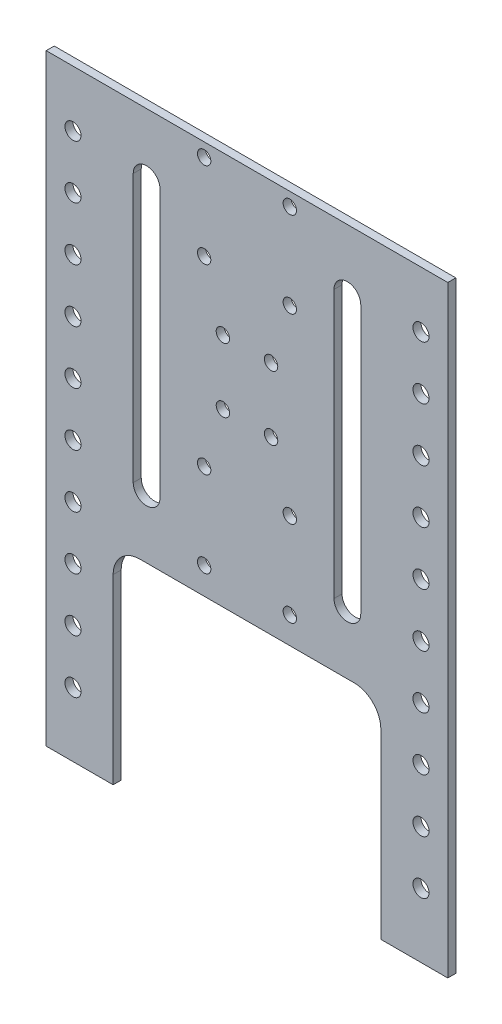
SolidWorks part; units mm, degrees
note: The reader was unsure of these and kept them because the rebuilt part matched: thickness of "Base-Flange1", "Sheet-Metal1", "Sheet-Metal2", "Sheet-Metal3".
material "Wrought Stainless Steel"
ref_plane "Front Plane" through (0, 0, 0) normal (0, 0, 1) x (1, 0, 0)
ref_plane "Top Plane" through (0, 0, 0) normal (0, 1, 0) x (1, 0, 0)
ref_plane "Right Plane" through (0, 0, 0) normal (1, 0, 0) x (0, 0, -1)
sketch "Sketch1" plane through (0, 0, 0) normal (0, 0, 1) x (1, 0, 0)
  line L1 (-75, -112.5) -> (75, -112.5)
  line L2 (-75, -112.5) -> (-75, 112.5)
  line L3 (-75, 112.5) -> (75, 112.5)
  line L4 (75, -112.5) -> (75, 112.5)
  line L5 (-75, -112.5) -> (75, 112.5) construction
  line L6 (-75, 112.5) -> (75, -112.5) construction
  point P0 (0, 0)
  dimension "D1" = 225
  dimension "D2" = 150
base flange "Base-Flange1" sketch "Sketch1" thickness 3 reverse thickness direction yes parameters "D1"=1
sketch "Sketch6" plane through (0, 0, 3) normal (0, 0, 1) x (1, 0, 0)
  line L0 (0, -1000) -> (0, 49000) construction
  line L2 (75, -112.5) -> (75, 112.5) construction
  line L3 (75, 112.5) -> (55, 112.5) construction
  line L4 (75, 112.5) -> (75, -112.5) construction
  line L5 (75, -112.5) -> (55, -112.5) construction
  line L6 (55, 112.5) -> (55, -112.5) construction
  line L7 (-75, -112.5) -> (75, -112.5) construction
  line L8 (-950, 107.5) -> (49050, 107.5) construction
  line L9 (-16, 75.5) -> (16, 75.5) construction
  line L10 (-16, 75.5) -> (-16, 107.5) construction
  line L11 (-16, 107.5) -> (16, 107.5) construction
  line L12 (16, 75.5) -> (16, 107.5) construction
  line L13 (-16, 75.5) -> (16, 107.5) construction
  line L14 (-16, 107.5) -> (16, 75.5) construction
  line L15 (16, 107.5) -> (-16, 107.5) construction
  line L16 (16, 107.5) -> (16, 75.5) construction
  line L17 (65, 91.5) -> (65, 71.5) construction
  line L18 (75, 112.5) -> (-75, 112.5) construction
  line L19 (-9, 29.5) -> (9, 29.5) construction
  line L20 (-9, 29.5) -> (-9, 53.5) construction
  line L21 (-9, 53.5) -> (9, 53.5) construction
  line L22 (9, 29.5) -> (9, 53.5) construction
  line L23 (-9, 29.5) -> (9, 53.5) construction
  line L24 (-9, 53.5) -> (9, 29.5) construction
  line L26 (9, 41.5) -> (-9, 41.5) construction
  line L27 (65, -800) -> (65, 49200) construction
  circle A0 centre (16, 107.5) radius 2.5
  circle A2 centre (-16, 107.5) radius 2.5
  circle A3 centre (-16, 75.5) radius 2.5
  circle A4 centre (16, 75.5) radius 2.5
  circle A5 centre (9, 53.5) radius 2.5
  circle A9 centre (16, 7.5) radius 2.5
  circle A10 centre (16, -24.5) radius 2.5
  circle A11 centre (-16, 7.5) radius 2.5
  circle A12 centre (-16, -24.5) radius 2.5
  circle A13 centre (65, 91.5) radius 3
  circle A14 centre (65, 71.5) radius 3
  circle A15 centre (65, 51.5) radius 3
  circle A16 centre (65, 31.5) radius 3
  circle A17 centre (65, 11.5) radius 3
  circle A18 centre (65, -8.5) radius 3
  circle A19 centre (65, -28.5) radius 3
  circle A20 centre (65, -48.5) radius 3
  circle A21 centre (-65, -48.5) radius 3
  circle A22 centre (-65, -28.5) radius 3
  circle A23 centre (-65, -8.5) radius 3
  circle A24 centre (-65, 11.5) radius 3
  circle A25 centre (-65, 31.5) radius 3
  circle A26 centre (-65, 51.5) radius 3
  circle A27 centre (-65, 71.5) radius 3
  circle A28 centre (-65, 91.5) radius 3
  circle A29 centre (9, 29.5) radius 2.5
  circle A30 centre (-9, 29.5) radius 2.5
  circle A31 centre (-9, 53.5) radius 2.5
  circle A32 centre (-65, -68.5) radius 3
  circle A33 centre (65, -68.5) radius 3
  circle A34 centre (-65, -88.5) radius 3
  circle A35 centre (65, -88.5) radius 3
  point P13 (0, 91.5)
  point P14 (0, 41.5)
  point P47 (0, 41.5)
  point P58 (65, 112.5)
  dimension "D5" = 5
  dimension "D14" = 5
  dimension "D19" = 20
  dimension "D20" = 6
  dimension "D17" = 32
  dimension "D1" = 20
  dimension "D3" = 32
  dimension "D4" = 32
  dimension "D8" = 32
  dimension "D9" = 32
  dimension "D11" = 50
  dimension "D12" = 18
  dimension "D13" = 24
  dimension "D18" = 3
  dimension "D23" = 20
  dimension "D15" = 5
  dimension "D16" = 16
  dimension "D6" = 2
  dimension "D7" = 2
  dimension "D22" = 8
extrude "Cut-Extrude1" cut sketch "Sketch6" against normal blind 10
sketch "Sketch7" plane through (0, 0, 3) normal (0, 0, 1) x (1, 0, 0)
  line L0 (0, -1000) -> (0, 49000) construction
  line L1 (-75, -112.5) -> (75, -112.5) construction
  line L2 (-50, -112.5) -> (50, -112.5)
  line L3 (-50, -112.5) -> (-50, -44.5)
  line L4 (-40, -34.5) -> (40, -34.5)
  line L5 (50, -112.5) -> (50, -44.5)
  line L6 (-75, 112.5) -> (-75, -112.5) construction
  line L7 (-37.5, -902.769) -> (-37.5, 49097.231) construction
  line L10 (-1107.0821, 39) -> (48892.9179, 39) construction
  line L11 (75, 112.5) -> (-75, 112.5) construction
  line L12 (-37.5, -11) -> (-37.5, 89) construction
  line L13 (-42.5, -11) -> (-42.5, 89)
  line L14 (-32.5, -11) -> (-32.5, 89)
  line L15 (37.5, -11) -> (37.5, 89) construction
  line L16 (42.5, -11) -> (42.5, 89)
  line L17 (32.5, -11) -> (32.5, 89)
  circle A0 centre (16, -24.5) radius 2.5 construction
  arc A1 (50, -44.5) -> (40, -34.5) centre (40, -44.5) ccw
  arc A2 (-50, -44.5) -> (-40, -34.5) centre (-40, -44.5) cw
  arc A3 (-42.5, -11) -> (-32.5, -11) centre (-37.5, -11) ccw
  arc A4 (-32.5, 89) -> (-42.5, 89) centre (-37.5, 89) ccw
  arc A5 (42.5, -11) -> (32.5, -11) centre (37.5, -11) cw
  arc A6 (32.5, 89) -> (42.5, 89) centre (37.5, 89) cw
  point P11 (0, -34.5)
  point P26 (-37.5, 39)
  point P33 (37.5, 39)
  dimension "D3" = 10
  dimension "D6" = 5
  dimension "D1" = 25
  dimension "D2" = 10
  dimension "D4" = 37.5
  dimension "D5" = 73.5
  dimension "D7" = 100
extrude "Cut-Extrude2" cut sketch "Sketch7" against normal blind 10
sketch "Bend-Lines1" [suppressed] plane through (0, 0, 0) normal (0, 1, 0) x (1, 0, 0)
sketch "Bounding-Box1" [suppressed] plane through (0, 0, 0) normal (0, 1, 0) x (1, 0, 0)
sheet metal parameters "Sheet-Metal1" thickness 3 parameters "D1"=1, "D7"=5
flat pattern "Flat-Pattern1" [suppressed]
sketch "Bend-Lines2" plane through (0, 0, 0) normal (0, 1, 0) x (1, 0, 0)
sketch3d "Bounding-Box2" [suppressed]
  line L0 (-50, 100, 0) -> (-50, -100, 0) construction
  line L1 (50, 100, 0) -> (50, -100, 0) construction
  line L2 (-50, 100, 0) -> (50, 100, 0) construction
  line L3 (-50, -100, 0) -> (50, -100, 0) construction
sheet metal parameters "Sheet-Metal2" thickness 3 parameters "D1"=1, "D7"=5
flat pattern "Flat-Pattern1"
sketch "Bend-Lines2" plane through (0, 0, 0) normal (0, 1, 0) x (1, 0, 0)
sketch3d "Bounding-Box2" [suppressed]
  line L0 (-75, 112.5, 0) -> (-75, -112.5, 0) construction
  line L1 (75, 112.5, 0) -> (75, -112.5, 0) construction
  line L2 (-75, 112.5, 0) -> (75, 112.5, 0) construction
  line L3 (-75, -112.5, 0) -> (75, -112.5, 0) construction
sheet metal parameters "Sheet-Metal3" thickness 3 parameters "D1"=1, "D7"=5
flat pattern "Flat-Pattern1"
sketch "Bend-Lines2" plane through (0, 0, 0) normal (0, 1, 0) x (1, 0, 0)
sketch3d "Bounding-Box2" [suppressed]
  line L0 (-75, 112.5, 0) -> (-75, -112.5, 0) construction
  line L1 (75, 112.5, 0) -> (75, -112.5, 0) construction
  line L2 (-75, 112.5, 0) -> (75, 112.5, 0) construction
  line L3 (-75, -112.5, 0) -> (75, -112.5, 0) construction
